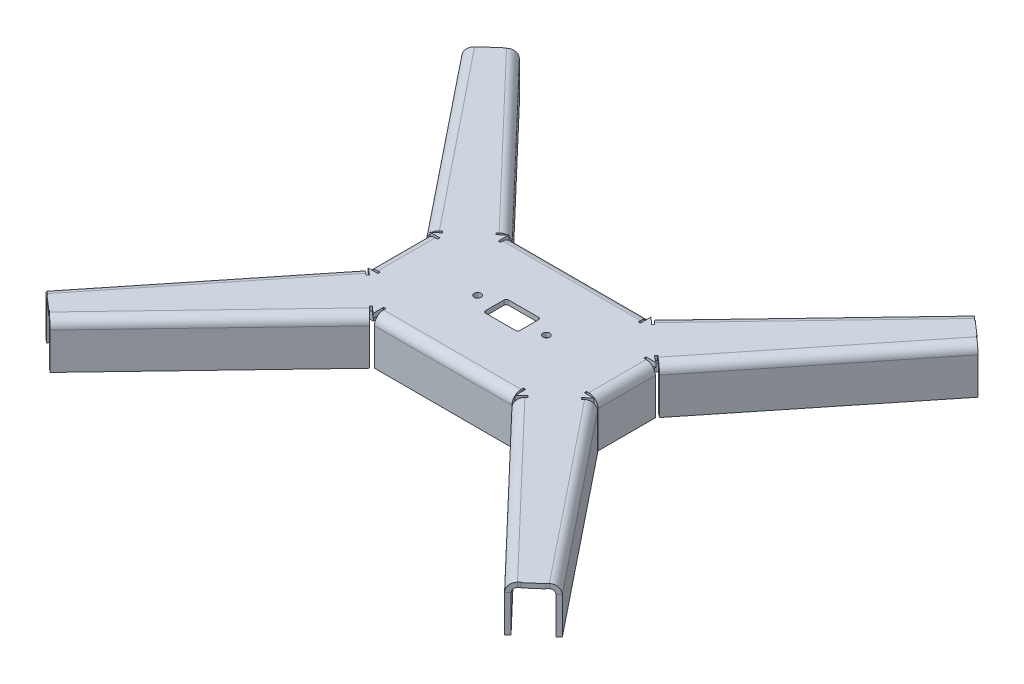
SolidWorks part; units mm, degrees
note: The reader was unsure of these and kept them because the rebuilt part matched: flange length of "Edge-Flange1", "Edge-Flange2", "Edge-Flange3", "Edge-Flange4", "Edge-Flange5", "Edge-Flange6", "Edge-Flange8", "Edge-Flange9", "Edge-Flange10", "Edge-Flange11", "Edge-Flange12", "Edge-Flange13".
material "1060 Alloy"
ref_plane "Front Plane" through (0, 0, 0) normal (0, 0, 1) x (1, 0, 0)
ref_plane "Top Plane" through (0, 0, 0) normal (0, 1, 0) x (1, 0, 0)
ref_plane "Right Plane" through (0, 0, 0) normal (1, 0, 0) x (0, 0, -1)
sketch "Sketch1" plane through (0, 0, 0) normal (0, 1, 0) x (1, 0, 0)
  line L0 (0, 0) -> (0, 30) construction
  line L1 (0, 0) -> (50, 0) construction
  line L2 (-30, 30) -> (30, 30)
  line L3 (30, 30) -> (50, 12.5) construction
  line L4 (50, 12.5) -> (50, -12.5)
  line L6 (-30, -30) -> (30, -30)
  line L9 (-50, 12.5) -> (-50, -12.5)
  line L10 (40, 21.25) -> (105.8505, 96.5077) construction
  line L11 (30, 30) -> (99.1363, 102.3826)
  line L12 (50, 12.5) -> (112.5646, 90.6328)
  line L13 (99.1363, 102.3826) -> (112.5646, 90.6328)
  line L14 (-40, 21.25) -> (-105.8505, 96.5077) construction
  line L15 (-30, 30) -> (-50, 12.5) construction
  line L16 (-99.1363, 102.3826) -> (-112.5646, 90.6328)
  line L17 (-50, 12.5) -> (-112.5646, 90.6328)
  line L18 (-30, 30) -> (-99.1363, 102.3826)
  line L19 (40, -21.25) -> (105.8505, -96.5077) construction
  line L20 (30, -30) -> (50, -12.5) construction
  line L21 (99.1363, -102.3826) -> (112.5646, -90.6328)
  line L22 (50, -12.5) -> (112.5646, -90.6328)
  line L23 (30, -30) -> (99.1363, -102.3826)
  line L24 (-30, -30) -> (-50, -12.5) construction
  line L25 (-40, -21.25) -> (-105.8505, -96.5077) construction
  line L26 (-30, -30) -> (-99.1363, -102.3826)
  line L27 (-50, -12.5) -> (-112.5646, -90.6328)
  line L28 (-99.1363, -102.3826) -> (-112.5646, -90.6328)
  dimension "D1" = 60
  dimension "D2" = 100
  dimension "D3" = 60
  dimension "D4" = 25
  dimension "D5" = 5
  dimension "D6" = 100
base flange "Base-Flange1" sketch "Sketch1" thickness 2 reverse thickness direction no parameters "D1"=2
edge flange "Edge-Flange1" sketch "Sketch8" flange angle 90 flange length 20 flange position material inside bend radius 2 thickness 2 relief rectangular parameters "D6"=10
sketch "Sketch8" plane through (0, -2, 30) normal (0, 0, 1) x (-1, 0, 0)
  line L0 (30, 0) -> (-30, 0) construction
  line L1 (30, 0) -> (-30, 0)
  line L2 (-30, 0) -> (-30, 18)
  line L3 (-30, 18) -> (30, 18)
  line L4 (30, 18) -> (30, 0)
bend "EdgeBend1" bend radius 2 bend angle 90 parameters "D5"=1
edge flange "Edge-Flange2" sketch "Sketch11" flange angle 90 flange length 20 flange position material inside bend radius 2 thickness 2 relief rectangular parameters "D6"=10
sketch "Sketch11" plane through (0, -2, -30) normal (0, 0, 1) x (-1, 0, 0)
  line L2 (-30, 0) -> (-30, 18)
  line L3 (-30, 18) -> (30, 18)
  line L4 (30, 18) -> (30, 0)
  line L5 (30, 0) -> (-30, 0) construction
  line L6 (30, 0) -> (-30, 0)
bend "EdgeBend2" bend radius 2 bend angle 90 parameters "D5"=2
edge flange "Edge-Flange3" sketch "Sketch19" flange angle 90 flange length 20 flange position material inside bend radius 2 thickness 2 relief rectangular parameters "D6"=10
sketch "Sketch19" plane through (50, -2, 0) normal (-1, 0, 0) x (0, 0, -1)
  line L2 (-12.5, 0) -> (-12.5, 18)
  line L3 (-12.5, 18) -> (12.5, 18)
  line L4 (12.5, 18) -> (12.5, 0)
  line L5 (12.5, 0) -> (-12.5, 0) construction
  line L6 (12.5, 0) -> (-12.5, 0)
bend "EdgeBend3" bend radius 2 bend angle 90 parameters "D5"=3
edge flange "Edge-Flange4" sketch "Sketch22" flange angle 90 flange length 20 flange position material inside bend radius 2 thickness 2 relief rectangular parameters "D6"=10
sketch "Sketch22" plane through (-50, -2, 0) normal (1, 0, 0) x (0, 0, 1)
  line L2 (-12.5, 0) -> (-12.5, 18)
  line L3 (-12.5, 18) -> (12.5, 18)
  line L4 (12.5, 18) -> (12.5, 0)
  line L5 (12.5, 0) -> (-12.5, 0) construction
  line L6 (12.5, 0) -> (-12.5, 0)
bend "EdgeBend4" bend radius 2 bend angle 90 parameters "D5"=4
edge flange "Edge-Flange5" sketch "Sketch26" flange angle 90 flange length 20 flange position material inside bend radius 2 thickness 2 relief rectangular parameters "D6"=10
sketch "Sketch26" plane through (24.3668, -2, -19.5116) normal (-0.7806, 0, 0.6251) x (-0.6251, 0, -0.7806)
  line L2 (-141.1051, 0) -> (-141.1051, 18)
  line L3 (-141.1051, 18) -> (-42.2909, 18)
  line L4 (-42.2909, 18) -> (-42.2909, 0)
  line L5 (-42.2909, 0) -> (-141.1051, 0) construction
  line L6 (-42.2909, 0) -> (-141.1051, 0)
bend "EdgeBend5" bend radius 2 bend angle 90 parameters "D5"=5
edge flange "Edge-Flange6" sketch "Sketch29" flange angle 90 flange length 20 flange position material inside bend radius 2 thickness 2 relief rectangular parameters "D6"=10
sketch "Sketch29" plane through (0.7036, -2, -0.672) normal (0.7231, 0, -0.6907) x (0.6907, 0, 0.7231)
  line L2 (43.863, 0) -> (43.863, 18)
  line L3 (43.863, 18) -> (142.5105, 18)
  line L4 (142.5105, 18) -> (142.5105, 0)
  line L5 (142.5105, 0) -> (43.863, 0) construction
  line L6 (142.5105, 0) -> (43.863, 0)
bend "EdgeBend6" bend radius 2 bend angle 90 parameters "D5"=6
edge flange "Edge-Flange8" sketch "Sketch39" flange angle 90 flange length 20 flange position material inside bend radius 2 thickness 2 relief rectangular parameters "D6"=10
sketch "Sketch39" plane through (24.3668, -2, 19.5116) normal (-0.7806, 0, -0.6251) x (0.6251, 0, -0.7806)
  line L2 (42.2909, 0) -> (42.2909, 18)
  line L3 (42.2909, 18) -> (141.1051, 18)
  line L4 (141.1051, 18) -> (141.1051, 0)
  line L5 (141.1051, 0) -> (42.2909, 0) construction
  line L6 (141.1051, 0) -> (42.2909, 0)
bend "EdgeBend8" bend radius 2 bend angle 90 parameters "D5"=7
edge flange "Edge-Flange9" sketch "Sketch42" flange angle 90 flange length 20 flange position material inside bend radius 2 thickness 2 relief rectangular parameters "D6"=10
sketch "Sketch42" plane through (0.7036, -2, 0.672) normal (0.7231, 0, 0.6907) x (-0.6907, 0, 0.7231)
  line L2 (-142.5105, 0) -> (-142.5105, 18)
  line L3 (-142.5105, 18) -> (-43.863, 18)
  line L4 (-43.863, 18) -> (-43.863, 0)
  line L5 (-43.863, 0) -> (-142.5105, 0) construction
  line L6 (-43.863, 0) -> (-142.5105, 0)
bend "EdgeBend9" bend radius 2 bend angle 90 parameters "D5"=8
edge flange "Edge-Flange10" sketch "Sketch45" flange angle 90 flange length 20 flange position material inside bend radius 2 thickness 2 relief rectangular parameters "D6"=10
sketch "Sketch45" plane through (-0.7036, -2, 0.672) normal (-0.7231, 0, 0.6907) x (-0.6907, 0, -0.7231)
  line L2 (43.863, 0) -> (43.863, 18)
  line L3 (43.863, 18) -> (142.5105, 18)
  line L4 (142.5105, 18) -> (142.5105, 0)
  line L5 (142.5105, 0) -> (43.863, 0) construction
  line L6 (142.5105, 0) -> (43.863, 0)
bend "EdgeBend10" bend radius 2 bend angle 90 parameters "D5"=9
edge flange "Edge-Flange11" sketch "Sketch48" flange angle 90 flange length 20 flange position material inside bend radius 2 thickness 2 relief rectangular parameters "D6"=10
sketch "Sketch48" plane through (-24.3668, -2, 19.5116) normal (0.7806, 0, -0.6251) x (0.6251, 0, 0.7806)
  line L2 (-141.1051, 0) -> (-141.1051, 18)
  line L3 (-141.1051, 18) -> (-42.2909, 18)
  line L4 (-42.2909, 18) -> (-42.2909, 0)
  line L5 (-42.2909, 0) -> (-141.1051, 0) construction
  line L6 (-42.2909, 0) -> (-141.1051, 0)
bend "EdgeBend11" bend radius 2 bend angle 90 parameters "D5"=10
edge flange "Edge-Flange12" sketch "Sketch51" flange angle 90 flange length 20 flange position material inside bend radius 2 thickness 2 relief rectangular parameters "D6"=10
sketch "Sketch51" plane through (-24.3668, -2, -19.5116) normal (0.7806, 0, 0.6251) x (-0.6251, 0, 0.7806)
  line L2 (42.2909, 0) -> (42.2909, 18)
  line L3 (42.2909, 18) -> (141.1051, 18)
  line L4 (141.1051, 18) -> (141.1051, 0)
  line L5 (141.1051, 0) -> (42.2909, 0) construction
  line L6 (141.1051, 0) -> (42.2909, 0)
bend "EdgeBend12" bend radius 2 bend angle 90 parameters "D5"=11
edge flange "Edge-Flange13" sketch "Sketch54" flange angle 90 flange length 20 flange position material inside bend radius 2 thickness 2 relief rectangular parameters "D6"=10
sketch "Sketch54" plane through (-0.7036, -2, -0.672) normal (-0.7231, 0, -0.6907) x (0.6907, 0, -0.7231)
  line L2 (-142.5105, 0) -> (-142.5105, 18)
  line L3 (-142.5105, 18) -> (-43.863, 18)
  line L4 (-43.863, 18) -> (-43.863, 0)
  line L5 (-43.863, 0) -> (-142.5105, 0) construction
  line L6 (-43.863, 0) -> (-142.5105, 0)
bend "EdgeBend13" bend radius 2 bend angle 90 parameters "D5"=12
sketch "Sketch58" plane through (0, 0, 0) normal (0, 1, 0) x (1, 0, 0)
  circle A0 centre (15, 0) radius 1.25 construction
  circle A1 centre (-15, 0) radius 1.25 construction
  circle A2 centre (15, 0) radius 1.25 construction
  circle A3 centre (-15, 0) radius 1.25 construction
  circle A4 centre (-15, 0) radius 1.5
  circle A5 centre (15, 0) radius 1.5
  dimension "D1" = 0.25
  dimension "D2" = 0.25
extrude "Cut-Extrude2" cut sketch "Sketch58" against normal through all normal cut yes
sketch "Sketch59" plane through (0, -2, 0) normal (0, -1, 0) x (1, 0, 0)
  line L1 (-7.5, -5) -> (7.5, -5)
  line L2 (-7.5, -5) -> (-7.5, 5)
  line L3 (-7.5, 5) -> (7.5, 5)
  line L4 (7.5, -5) -> (7.5, 5)
  line L5 (-7.5, -5) -> (7.5, 5) construction
  line L6 (-7.5, 5) -> (7.5, -5) construction
  point P0 (0, 0)
  dimension "D1" = 10
  dimension "D2" = 15
extrude "Cut-Extrude3" cut sketch "Sketch59" against normal through all normal cut yes
fillet "Fillet1" radius 1 4 edges at (-7.5, -1, 5) (-7.5, -1, -5) (7.5, -1, -5) (7.5, -1, 5)
sketch "Bend-Lines1" [suppressed] plane through (0, 0, 0) normal (0, 1, 0) x (1, 0, 0)
sketch "Bounding-Box1" [suppressed] plane through (0, 0, 0) normal (0, 1, 0) x (1, 0, 0)
sheet metal parameters "Sheet-Metal1" thickness 2 parameters "D1"=2
flat pattern "Flat-Pattern1" [suppressed]
sketch "Bend-Lines2" plane through (0, 0, 0) normal (0, 1, 0) x (1, 0, 0)
sketch3d "Bounding-Box2" [suppressed]
  line L0 (-50, 30, 0) -> (50, 30, 0) construction
  line L1 (-50, -30, 0) -> (50, -30, 0) construction
  line L2 (-50, 30, 0) -> (-50, -30, 0) construction
  line L3 (50, 30, 0) -> (50, -30, 0) construction
sheet metal parameters "Sheet-Metal2" thickness 2 parameters "D1"=2
flat pattern "Flat-Pattern1"
sketch "Bend-Lines2" plane through (0, 0, 0) normal (0, 1, 0) x (1, 0, 0)
  line L0 (-30, -28.3562) -> (30, -28.3562) construction
  line L1 (-30, -28.3562) -> (30, -28.3562) construction
sketch3d "Bounding-Box2" [suppressed]
  line L0 (50, 30, 0) -> (-50, 30, 0) construction
  line L1 (50, -46.7124, 0) -> (-50, -46.7124, 0) construction
  line L2 (50, 30, 0) -> (50, -46.7124, 0) construction
  line L3 (-50, 30, 0) -> (-50, -46.7124, 0) construction
bend of the flat pattern "Flatten-<EdgeBend1>1"
sheet metal parameters "Sheet-Metal3" thickness 2 parameters "D1"=2
flat pattern "Flat-Pattern1" [suppressed]
sketch "Bend-Lines2" plane through (0, 0, 0) normal (0, 1, 0) x (1, 0, 0)
  line L0 (-30, -28.3562) -> (30, -28.3562) construction
  line L1 (-30, -28.3562) -> (30, -28.3562) construction
  line L2 (30, 28.3562) -> (-30, 28.3562) construction
  line L3 (30, 28.3562) -> (-30, 28.3562) construction
sketch3d "Bounding-Box2" [suppressed]
  line L0 (50, 46.7124, 0) -> (-50, 46.7124, 0) construction
  line L1 (50, -46.7124, 0) -> (-50, -46.7124, 0) construction
  line L2 (50, 46.7124, 0) -> (50, -46.7124, 0) construction
  line L3 (-50, 46.7124, 0) -> (-50, -46.7124, 0) construction
bend of the flat pattern "Flatten-<EdgeBend1>1"
bend of the flat pattern "Flatten-<EdgeBend2>1"
sheet metal parameters "Sheet-Metal4" thickness 2 parameters "D1"=2
flat pattern "Flat-Pattern1" [suppressed]
sketch "Bend-Lines2" plane through (0, 0, 0) normal (0, 1, 0) x (1, 0, 0)
  line L0 (-30, -28.3562) -> (30, -28.3562) construction
  line L1 (-30, -28.3562) -> (30, -28.3562) construction
  line L2 (30, 28.3562) -> (-30, 28.3562) construction
  line L3 (30, 28.3562) -> (-30, 28.3562) construction
  line L4 (48.3562, -12.5) -> (48.3562, 12.5) construction
  line L5 (48.3562, -12.5) -> (48.3562, 12.5) construction
sketch3d "Bounding-Box2" [suppressed]
  line L0 (66.7124, 46.7124, 0) -> (-50, 46.7124, 0) construction
  line L1 (66.7124, -46.7124, 0) -> (-50, -46.7124, 0) construction
  line L2 (66.7124, 46.7124, 0) -> (66.7124, -46.7124, 0) construction
  line L3 (-50, 46.7124, 0) -> (-50, -46.7124, 0) construction
bend of the flat pattern "Flatten-<EdgeBend1>1"
bend of the flat pattern "Flatten-<EdgeBend3>1"
bend of the flat pattern "Flatten-<EdgeBend2>1"
sheet metal parameters "Sheet-Metal5" thickness 2 parameters "D1"=2
flat pattern "Flat-Pattern1" [suppressed]
sketch "Bend-Lines2" plane through (0, 0, 0) normal (0, 1, 0) x (1, 0, 0)
  line L0 (-30, -28.3562) -> (30, -28.3562) construction
  line L1 (-30, -28.3562) -> (30, -28.3562) construction
  line L2 (30, 28.3562) -> (-30, 28.3562) construction
  line L3 (30, 28.3562) -> (-30, 28.3562) construction
  line L4 (48.3562, -12.5) -> (48.3562, 12.5) construction
  line L5 (48.3562, -12.5) -> (48.3562, 12.5) construction
  line L6 (-48.3562, 12.5) -> (-48.3562, -12.5) construction
  line L7 (-48.3562, 12.5) -> (-48.3562, -12.5) construction
sketch3d "Bounding-Box2" [suppressed]
  line L0 (110.9178, -100.9416, 0) -> (-110.9178, -100.9416, 0) construction
  line L1 (110.9178, 100.9416, 0) -> (-110.9178, 100.9416, 0) construction
  line L2 (110.9178, -100.9416, 0) -> (110.9178, 100.9416, 0) construction
  line L3 (-110.9178, -100.9416, 0) -> (-110.9178, 100.9416, 0) construction
bend of the flat pattern "Flatten-<EdgeBend1>1"
bend of the flat pattern "Flatten-<EdgeBend3>1"
bend of the flat pattern "Flatten-<EdgeBend4>1"
bend of the flat pattern "Flatten-<EdgeBend2>1"
sheet metal parameters "Sheet-Metal6" thickness 2 parameters "D1"=2
flat pattern "Flat-Pattern1" [suppressed]
sketch "Bend-Lines2" plane through (0, 0, 0) normal (0, 1, 0) x (1, 0, 0)
  line L0 (-30, -28.3562) -> (30, -28.3562) construction
  line L1 (-30, -28.3562) -> (30, -28.3562) construction
  line L2 (30, 28.3562) -> (-30, 28.3562) construction
  line L3 (30, 28.3562) -> (-30, 28.3562) construction
  line L4 (48.3562, -12.5) -> (48.3562, 12.5) construction
  line L5 (48.3562, -12.5) -> (48.3562, 12.5) construction
  line L6 (-48.3562, 12.5) -> (-48.3562, -12.5) construction
  line L7 (-48.3562, 12.5) -> (-48.3562, -12.5) construction
  line L8 (109.6126, -93.073) -> (49.4603, -14.4992) construction
  line L9 (109.6126, -93.073) -> (49.4603, -14.4992) construction
sketch3d "Bounding-Box2" [suppressed]
  line L0 (124.188, -100.9416, 0) -> (-110.9178, -100.9416, 0) construction
  line L1 (124.188, 100.9416, 0) -> (-110.9178, 100.9416, 0) construction
  line L2 (124.188, -100.9416, 0) -> (124.188, 100.9416, 0) construction
  line L3 (-110.9178, -100.9416, 0) -> (-110.9178, 100.9416, 0) construction
bend of the flat pattern "Flatten-<EdgeBend1>1"
bend of the flat pattern "Flatten-<EdgeBend3>1"
bend of the flat pattern "Flatten-<EdgeBend4>1"
bend of the flat pattern "Flatten-<EdgeBend5>1"
bend of the flat pattern "Flatten-<EdgeBend2>1"
sheet metal parameters "Sheet-Metal7" thickness 2 parameters "D1"=2
flat pattern "Flat-Pattern1" [suppressed]
sketch "Bend-Lines2" plane through (0, 0, 0) normal (0, 1, 0) x (1, 0, 0)
  line L0 (-30, -28.3562) -> (30, -28.3562) construction
  line L1 (-30, -28.3562) -> (30, -28.3562) construction
  line L2 (30, 28.3562) -> (-30, 28.3562) construction
  line L3 (30, 28.3562) -> (-30, 28.3562) construction
  line L4 (48.3562, -12.5) -> (48.3562, 12.5) construction
  line L5 (48.3562, -12.5) -> (48.3562, 12.5) construction
  line L6 (-48.3562, 12.5) -> (-48.3562, -12.5) construction
  line L7 (-48.3562, 12.5) -> (-48.3562, -12.5) construction
  line L8 (109.6126, -93.073) -> (49.4603, -14.4992) construction
  line L9 (109.6126, -93.073) -> (49.4603, -14.4992) construction
  line L10 (32.1636, -29.8412) -> (101.9468, -99.7806) construction
  line L11 (32.1636, -29.8412) -> (101.9468, -99.7806) construction
sketch3d "Bounding-Box2" [suppressed]
  line L0 (124.188, -112.7458, 0) -> (-110.9178, -112.7458, 0) construction
  line L1 (124.188, 100.9416, 0) -> (-110.9178, 100.9416, 0) construction
  line L2 (124.188, -112.7458, 0) -> (124.188, 100.9416, 0) construction
  line L3 (-110.9178, -112.7458, 0) -> (-110.9178, 100.9416, 0) construction
bend of the flat pattern "Flatten-<EdgeBend1>1"
bend of the flat pattern "Flatten-<EdgeBend3>1"
bend of the flat pattern "Flatten-<EdgeBend4>1"
bend of the flat pattern "Flatten-<EdgeBend5>1"
bend of the flat pattern "Flatten-<EdgeBend6>1"
bend of the flat pattern "Flatten-<EdgeBend2>1"
sheet metal parameters "Sheet-Metal9" thickness 2 parameters "D1"=2
flat pattern "Flat-Pattern1" [suppressed]
sketch "Bend-Lines2" plane through (0, 0, 0) normal (0, 1, 0) x (1, 0, 0)
  line L0 (-30, -28.3562) -> (30, -28.3562) construction
  line L1 (-30, -28.3562) -> (30, -28.3562) construction
  line L2 (30, 28.3562) -> (-30, 28.3562) construction
  line L3 (30, 28.3562) -> (-30, 28.3562) construction
  line L4 (48.3562, -12.5) -> (48.3562, 12.5) construction
  line L5 (48.3562, -12.5) -> (48.3562, 12.5) construction
  line L6 (-48.3562, 12.5) -> (-48.3562, -12.5) construction
  line L7 (-48.3562, 12.5) -> (-48.3562, -12.5) construction
  line L8 (109.6126, -93.073) -> (49.4603, -14.4992) construction
  line L9 (109.6126, -93.073) -> (49.4603, -14.4992) construction
  line L10 (32.1636, -29.8412) -> (101.9468, -99.7806) construction
  line L11 (32.1636, -29.8412) -> (101.9468, -99.7806) construction
  line L12 (49.4603, 14.4992) -> (109.6126, 93.073) construction
  line L13 (49.4603, 14.4992) -> (109.6126, 93.073) construction
sketch3d "Bounding-Box2" [suppressed]
  line L0 (124.188, -112.7458, 0) -> (-110.9178, -112.7458, 0) construction
  line L1 (124.188, 100.9416, 0) -> (-110.9178, 100.9416, 0) construction
  line L2 (124.188, -112.7458, 0) -> (124.188, 100.9416, 0) construction
  line L3 (-110.9178, -112.7458, 0) -> (-110.9178, 100.9416, 0) construction
bend of the flat pattern "Flatten-<EdgeBend1>1"
bend of the flat pattern "Flatten-<EdgeBend3>1"
bend of the flat pattern "Flatten-<EdgeBend4>1"
bend of the flat pattern "Flatten-<EdgeBend5>1"
bend of the flat pattern "Flatten-<EdgeBend6>1"
bend of the flat pattern "Flatten-<EdgeBend8>1"
bend of the flat pattern "Flatten-<EdgeBend2>1"
sheet metal parameters "Sheet-Metal10" thickness 2 parameters "D1"=2
flat pattern "Flat-Pattern1" [suppressed]
sketch "Bend-Lines2" plane through (0, 0, 0) normal (0, 1, 0) x (1, 0, 0)
  line L0 (-30, -28.3562) -> (30, -28.3562) construction
  line L1 (-30, -28.3562) -> (30, -28.3562) construction
  line L2 (30, 28.3562) -> (-30, 28.3562) construction
  line L3 (30, 28.3562) -> (-30, 28.3562) construction
  line L4 (48.3562, -12.5) -> (48.3562, 12.5) construction
  line L5 (48.3562, -12.5) -> (48.3562, 12.5) construction
  line L6 (-48.3562, 12.5) -> (-48.3562, -12.5) construction
  line L7 (-48.3562, 12.5) -> (-48.3562, -12.5) construction
  line L8 (109.6126, -93.073) -> (49.4603, -14.4992) construction
  line L9 (109.6126, -93.073) -> (49.4603, -14.4992) construction
  line L10 (32.1636, -29.8412) -> (101.9468, -99.7806) construction
  line L11 (32.1636, -29.8412) -> (101.9468, -99.7806) construction
  line L12 (49.4603, 14.4992) -> (109.6126, 93.073) construction
  line L13 (49.4603, 14.4992) -> (109.6126, 93.073) construction
  line L14 (101.9468, 99.7806) -> (32.1636, 29.8412) construction
  line L15 (101.9468, 99.7806) -> (32.1636, 29.8412) construction
sketch3d "Bounding-Box2" [suppressed]
  line L0 (124.188, -112.7458, 0) -> (-110.9178, -112.7458, 0) construction
  line L1 (124.188, 112.7458, 0) -> (-110.9178, 112.7458, 0) construction
  line L2 (124.188, -112.7458, 0) -> (124.188, 112.7458, 0) construction
  line L3 (-110.9178, -112.7458, 0) -> (-110.9178, 112.7458, 0) construction
bend of the flat pattern "Flatten-<EdgeBend1>1"
bend of the flat pattern "Flatten-<EdgeBend3>1"
bend of the flat pattern "Flatten-<EdgeBend4>1"
bend of the flat pattern "Flatten-<EdgeBend5>1"
bend of the flat pattern "Flatten-<EdgeBend6>1"
bend of the flat pattern "Flatten-<EdgeBend8>1"
bend of the flat pattern "Flatten-<EdgeBend9>1"
bend of the flat pattern "Flatten-<EdgeBend2>1"
sheet metal parameters "Sheet-Metal11" thickness 2 parameters "D1"=2
flat pattern "Flat-Pattern1"
sketch "Bend-Lines2" plane through (0, 0, 0) normal (0, 1, 0) x (1, 0, 0)
  line L0 (-30, -28.3562) -> (30, -28.3562) construction
  line L1 (-30, -28.3562) -> (30, -28.3562) construction
  line L2 (30, 28.3562) -> (-30, 28.3562) construction
  line L3 (30, 28.3562) -> (-30, 28.3562) construction
  line L4 (48.3562, -12.5) -> (48.3562, 12.5) construction
  line L5 (48.3562, -12.5) -> (48.3562, 12.5) construction
  line L6 (-48.3562, 12.5) -> (-48.3562, -12.5) construction
  line L7 (-48.3562, 12.5) -> (-48.3562, -12.5) construction
  line L8 (111.2815, -91.6602) -> (49.5176, -14.5275) construction
  line L9 (111.2815, -91.6602) -> (49.5176, -14.5275) construction
  line L10 (32.1887, -29.9116) -> (100.325, -101.2472) construction
  line L11 (32.1887, -29.9116) -> (100.325, -101.2472) construction
  line L12 (49.5176, 14.5275) -> (111.2815, 91.6602) construction
  line L13 (49.5176, 14.5275) -> (111.2815, 91.6602) construction
  line L14 (100.325, 101.2472) -> (32.1887, 29.9116) construction
  line L15 (100.325, 101.2472) -> (32.1887, 29.9116) construction
  line L16 (-32.1887, 29.9116) -> (-100.325, 101.2472) construction
  line L17 (-32.1887, 29.9116) -> (-100.325, 101.2472) construction
sketch3d "Bounding-Box2" [suppressed]
  line L0 (125.6101, -113.9259, 0) -> (-112.5646, -113.9259, 0) construction
  line L1 (125.6101, 113.9259, 0) -> (-112.5646, 113.9259, 0) construction
  line L2 (125.6101, -113.9259, 0) -> (125.6101, 113.9259, 0) construction
  line L3 (-112.5646, -113.9259, 0) -> (-112.5646, 113.9259, 0) construction
bend of the flat pattern "Flatten-<EdgeBend1>1"
bend of the flat pattern "Flatten-<EdgeBend3>1"
bend of the flat pattern "Flatten-<EdgeBend4>1"
bend of the flat pattern "Flatten-<EdgeBend5>1"
bend of the flat pattern "Flatten-<EdgeBend6>1"
bend of the flat pattern "Flatten-<EdgeBend8>1"
bend of the flat pattern "Flatten-<EdgeBend9>1"
bend of the flat pattern "Flatten-<EdgeBend10>1"
bend of the flat pattern "Flatten-<EdgeBend2>1"
sheet metal parameters "Sheet-Metal12" thickness 2 parameters "D1"=2
flat pattern "Flat-Pattern1"
sketch "Bend-Lines2" plane through (0, 0, 0) normal (0, 1, 0) x (1, 0, 0)
  line L0 (-30, -28.3562) -> (30, -28.3562) construction
  line L1 (-30, -28.3562) -> (30, -28.3562) construction
  line L2 (30, 28.3562) -> (-30, 28.3562) construction
  line L3 (30, 28.3562) -> (-30, 28.3562) construction
  line L4 (48.3562, -12.5) -> (48.3562, 12.5) construction
  line L5 (48.3562, -12.5) -> (48.3562, 12.5) construction
  line L6 (-48.3562, 12.5) -> (-48.3562, -12.5) construction
  line L7 (-48.3562, 12.5) -> (-48.3562, -12.5) construction
  line L8 (111.2815, -91.6602) -> (49.5176, -14.5275) construction
  line L9 (111.2815, -91.6602) -> (49.5176, -14.5275) construction
  line L10 (32.1887, -29.9116) -> (100.325, -101.2472) construction
  line L11 (32.1887, -29.9116) -> (100.325, -101.2472) construction
  line L12 (49.5176, 14.5275) -> (111.2815, 91.6602) construction
  line L13 (49.5176, 14.5275) -> (111.2815, 91.6602) construction
  line L14 (100.325, 101.2472) -> (32.1887, 29.9116) construction
  line L15 (100.325, 101.2472) -> (32.1887, 29.9116) construction
  line L16 (-32.1887, 29.9116) -> (-100.325, 101.2472) construction
  line L17 (-32.1887, 29.9116) -> (-100.325, 101.2472) construction
  line L18 (-112.8427, 90.4101) -> (-51.0788, 13.2774) construction
  line L19 (-112.8427, 90.4101) -> (-51.0788, 13.2774) construction
sketch3d "Bounding-Box2" [suppressed]
  line L0 (125.6101, -113.9259, 0) -> (-127.1712, -113.9259, 0) construction
  line L1 (125.6101, 113.9259, 0) -> (-127.1712, 113.9259, 0) construction
  line L2 (125.6101, -113.9259, 0) -> (125.6101, 113.9259, 0) construction
  line L3 (-127.1712, -113.9259, 0) -> (-127.1712, 113.9259, 0) construction
bend of the flat pattern "Flatten-<EdgeBend1>1"
bend of the flat pattern "Flatten-<EdgeBend3>1"
bend of the flat pattern "Flatten-<EdgeBend4>1"
bend of the flat pattern "Flatten-<EdgeBend5>1"
bend of the flat pattern "Flatten-<EdgeBend6>1"
bend of the flat pattern "Flatten-<EdgeBend8>1"
bend of the flat pattern "Flatten-<EdgeBend9>1"
bend of the flat pattern "Flatten-<EdgeBend10>1"
bend of the flat pattern "Flatten-<EdgeBend2>1"
bend of the flat pattern "Flatten-<EdgeBend11>1"
sheet metal parameters "Sheet-Metal13" thickness 2 parameters "D1"=2
flat pattern "Flat-Pattern1"
sketch "Bend-Lines2" plane through (0, 0, 0) normal (0, 1, 0) x (1, 0, 0)
  line L0 (-30, -28.3562) -> (30, -28.3562) construction
  line L1 (-30, -28.3562) -> (30, -28.3562) construction
  line L2 (30, 28.3562) -> (-30, 28.3562) construction
  line L3 (30, 28.3562) -> (-30, 28.3562) construction
  line L4 (48.3562, -12.5) -> (48.3562, 12.5) construction
  line L5 (48.3562, -12.5) -> (48.3562, 12.5) construction
  line L6 (-48.3562, 12.5) -> (-48.3562, -12.5) construction
  line L7 (-48.3562, 12.5) -> (-48.3562, -12.5) construction
  line L8 (111.2815, -91.6602) -> (49.5176, -14.5275) construction
  line L9 (111.2815, -91.6602) -> (49.5176, -14.5275) construction
  line L10 (32.1887, -29.9116) -> (100.325, -101.2472) construction
  line L11 (32.1887, -29.9116) -> (100.325, -101.2472) construction
  line L12 (49.5176, 14.5275) -> (111.2815, 91.6602) construction
  line L13 (49.5176, 14.5275) -> (111.2815, 91.6602) construction
  line L14 (100.325, 101.2472) -> (32.1887, 29.9116) construction
  line L15 (100.325, 101.2472) -> (32.1887, 29.9116) construction
  line L16 (-32.1887, 29.9116) -> (-100.325, 101.2472) construction
  line L17 (-32.1887, 29.9116) -> (-100.325, 101.2472) construction
  line L18 (-112.8427, 90.4101) -> (-51.0788, 13.2774) construction
  line L19 (-112.8427, 90.4101) -> (-51.0788, 13.2774) construction
  line L20 (-51.0788, -13.2774) -> (-112.8427, -90.4101) construction
  line L21 (-51.0788, -13.2774) -> (-112.8427, -90.4101) construction
sketch3d "Bounding-Box2" [suppressed]
  line L0 (125.6101, -113.9259, 0) -> (-127.1712, -113.9259, 0) construction
  line L1 (125.6101, 113.9259, 0) -> (-127.1712, 113.9259, 0) construction
  line L2 (125.6101, -113.9259, 0) -> (125.6101, 113.9259, 0) construction
  line L3 (-127.1712, -113.9259, 0) -> (-127.1712, 113.9259, 0) construction
bend of the flat pattern "Flatten-<EdgeBend1>1"
bend of the flat pattern "Flatten-<EdgeBend3>1"
bend of the flat pattern "Flatten-<EdgeBend4>1"
bend of the flat pattern "Flatten-<EdgeBend5>1"
bend of the flat pattern "Flatten-<EdgeBend6>1"
bend of the flat pattern "Flatten-<EdgeBend8>1"
bend of the flat pattern "Flatten-<EdgeBend9>1"
bend of the flat pattern "Flatten-<EdgeBend10>1"
bend of the flat pattern "Flatten-<EdgeBend2>1"
bend of the flat pattern "Flatten-<EdgeBend11>1"
bend of the flat pattern "Flatten-<EdgeBend12>1"
sheet metal parameters "Sheet-Metal14" thickness 2 parameters "D1"=2
flat pattern "Flat-Pattern1"
sketch "Bend-Lines2" plane through (0, 0, 0) normal (0, 1, 0) x (1, 0, 0)
  line L0 (-30, -28.3562) -> (30, -28.3562) construction
  line L1 (-30, -28.3562) -> (30, -28.3562) construction
  line L2 (30, 28.3562) -> (-30, 28.3562) construction
  line L3 (30, 28.3562) -> (-30, 28.3562) construction
  line L4 (48.3562, -12.5) -> (48.3562, 12.5) construction
  line L5 (48.3562, -12.5) -> (48.3562, 12.5) construction
  line L6 (-48.3562, 12.5) -> (-48.3562, -12.5) construction
  line L7 (-48.3562, 12.5) -> (-48.3562, -12.5) construction
  line L8 (111.2815, -91.6602) -> (49.5176, -14.5275) construction
  line L9 (111.2815, -91.6602) -> (49.5176, -14.5275) construction
  line L10 (32.1887, -29.9116) -> (100.325, -101.2472) construction
  line L11 (32.1887, -29.9116) -> (100.325, -101.2472) construction
  line L12 (49.5176, 14.5275) -> (111.2815, 91.6602) construction
  line L13 (49.5176, 14.5275) -> (111.2815, 91.6602) construction
  line L14 (100.325, 101.2472) -> (32.1887, 29.9116) construction
  line L15 (100.325, 101.2472) -> (32.1887, 29.9116) construction
  line L16 (-32.1887, 29.9116) -> (-100.325, 101.2472) construction
  line L17 (-32.1887, 29.9116) -> (-100.325, 101.2472) construction
  line L18 (-112.8427, 90.4101) -> (-51.0788, 13.2774) construction
  line L19 (-112.8427, 90.4101) -> (-51.0788, 13.2774) construction
  line L20 (-51.0788, -13.2774) -> (-112.8427, -90.4101) construction
  line L21 (-51.0788, -13.2774) -> (-112.8427, -90.4101) construction
  line L22 (-98.8787, -102.6286) -> (-30.7424, -31.293) construction
  line L23 (-98.8787, -102.6286) -> (-30.7424, -31.293) construction
sketch3d "Bounding-Box2" [suppressed]
  line L0 (125.6101, -115.3073, 0) -> (-127.1712, -115.3073, 0) construction
  line L1 (125.6101, 113.9259, 0) -> (-127.1712, 113.9259, 0) construction
  line L2 (125.6101, -115.3073, 0) -> (125.6101, 113.9259, 0) construction
  line L3 (-127.1712, -115.3073, 0) -> (-127.1712, 113.9259, 0) construction
bend of the flat pattern "Flatten-<EdgeBend1>1"
bend of the flat pattern "Flatten-<EdgeBend3>1"
bend of the flat pattern "Flatten-<EdgeBend4>1"
bend of the flat pattern "Flatten-<EdgeBend5>1"
bend of the flat pattern "Flatten-<EdgeBend6>1"
bend of the flat pattern "Flatten-<EdgeBend8>1"
bend of the flat pattern "Flatten-<EdgeBend9>1"
bend of the flat pattern "Flatten-<EdgeBend10>1"
bend of the flat pattern "Flatten-<EdgeBend2>1"
bend of the flat pattern "Flatten-<EdgeBend11>1"
bend of the flat pattern "Flatten-<EdgeBend12>1"
bend of the flat pattern "Flatten-<EdgeBend13>1"
sheet metal parameters "Sheet-Metal19" thickness 2 parameters "D1"=2
flat pattern "Flat-Pattern1"
sketch "Bend-Lines2" plane through (0, 0, 0) normal (0, 1, 0) x (1, 0, 0)
  line L0 (-30, -28.3562) -> (30, -28.3562) construction
  line L1 (-30, -28.3562) -> (30, -28.3562) construction
  line L2 (30, 28.3562) -> (-30, 28.3562) construction
  line L3 (30, 28.3562) -> (-30, 28.3562) construction
  line L4 (48.3562, -12.5) -> (48.3562, 12.5) construction
  line L5 (48.3562, -12.5) -> (48.3562, 12.5) construction
  line L6 (-48.3562, 12.5) -> (-48.3562, -12.5) construction
  line L7 (-48.3562, 12.5) -> (-48.3562, -12.5) construction
  line L8 (111.2815, -91.6602) -> (49.5176, -14.5275) construction
  line L9 (111.2815, -91.6602) -> (49.5176, -14.5275) construction
  line L10 (32.1887, -29.9116) -> (100.325, -101.2472) construction
  line L11 (32.1887, -29.9116) -> (100.325, -101.2472) construction
  line L12 (49.5176, 14.5275) -> (111.2815, 91.6602) construction
  line L13 (49.5176, 14.5275) -> (111.2815, 91.6602) construction
  line L14 (100.325, 101.2472) -> (32.1887, 29.9116) construction
  line L15 (100.325, 101.2472) -> (32.1887, 29.9116) construction
  line L16 (-32.1887, 29.9116) -> (-100.325, 101.2472) construction
  line L17 (-32.1887, 29.9116) -> (-100.325, 101.2472) construction
  line L18 (-111.2815, 91.6602) -> (-49.5176, 14.5275) construction
  line L19 (-111.2815, 91.6602) -> (-49.5176, 14.5275) construction
  line L20 (-49.5176, -14.5275) -> (-111.2815, -91.6602) construction
  line L21 (-49.5176, -14.5275) -> (-111.2815, -91.6602) construction
  line L22 (-100.325, -101.2472) -> (-32.1887, -29.9116) construction
  line L23 (-100.325, -101.2472) -> (-32.1887, -29.9116) construction
sketch3d "Bounding-Box2" [suppressed]
  line L0 (125.6101, -113.9259, 0) -> (-125.6101, -113.9259, 0) construction
  line L1 (125.6101, 113.9259, 0) -> (-125.6101, 113.9259, 0) construction
  line L2 (125.6101, -113.9259, 0) -> (125.6101, 113.9259, 0) construction
  line L3 (-125.6101, -113.9259, 0) -> (-125.6101, 113.9259, 0) construction
bend of the flat pattern "Flatten-<EdgeBend1>1"
bend of the flat pattern "Flatten-<EdgeBend3>1"
bend of the flat pattern "Flatten-<EdgeBend4>1"
bend of the flat pattern "Flatten-<EdgeBend5>1"
bend of the flat pattern "Flatten-<EdgeBend6>1"
bend of the flat pattern "Flatten-<EdgeBend8>1"
bend of the flat pattern "Flatten-<EdgeBend9>1"
bend of the flat pattern "Flatten-<EdgeBend10>1"
bend of the flat pattern "Flatten-<EdgeBend2>1"
bend of the flat pattern "Flatten-<EdgeBend11>1"
bend of the flat pattern "Flatten-<EdgeBend12>1"
bend of the flat pattern "Flatten-<EdgeBend13>1"
sheet metal parameters "Sheet-Metal20" thickness 2 parameters "D1"=2
flat pattern "Flat-Pattern1"
sketch "Bend-Lines2" plane through (0, 0, 0) normal (0, 1, 0) x (1, 0, 0)
  line L0 (-30, -28.3562) -> (30, -28.3562) construction
  line L1 (-30, -28.3562) -> (30, -28.3562) construction
  line L2 (30, 28.3562) -> (-30, 28.3562) construction
  line L3 (30, 28.3562) -> (-30, 28.3562) construction
  line L4 (48.3562, -12.5) -> (48.3562, 12.5) construction
  line L5 (48.3562, -12.5) -> (48.3562, 12.5) construction
  line L6 (-48.3562, 12.5) -> (-48.3562, -12.5) construction
  line L7 (-48.3562, 12.5) -> (-48.3562, -12.5) construction
  line L8 (111.2815, -91.6602) -> (49.5176, -14.5275) construction
  line L9 (111.2815, -91.6602) -> (49.5176, -14.5275) construction
  line L10 (32.1887, -29.9116) -> (100.325, -101.2472) construction
  line L11 (32.1887, -29.9116) -> (100.325, -101.2472) construction
  line L12 (49.5176, 14.5275) -> (111.2815, 91.6602) construction
  line L13 (49.5176, 14.5275) -> (111.2815, 91.6602) construction
  line L14 (100.325, 101.2472) -> (32.1887, 29.9116) construction
  line L15 (100.325, 101.2472) -> (32.1887, 29.9116) construction
  line L16 (-32.1887, 29.9116) -> (-100.325, 101.2472) construction
  line L17 (-32.1887, 29.9116) -> (-100.325, 101.2472) construction
  line L18 (-111.2815, 91.6602) -> (-49.5176, 14.5275) construction
  line L19 (-111.2815, 91.6602) -> (-49.5176, 14.5275) construction
  line L20 (-49.5176, -14.5275) -> (-111.2815, -91.6602) construction
  line L21 (-49.5176, -14.5275) -> (-111.2815, -91.6602) construction
  line L22 (-100.325, -101.2472) -> (-32.1887, -29.9116) construction
  line L23 (-100.325, -101.2472) -> (-32.1887, -29.9116) construction
sketch3d "Bounding-Box2" [suppressed]
  line L0 (125.6101, -113.9259, 0) -> (-125.6101, -113.9259, 0) construction
  line L1 (125.6101, 113.9259, 0) -> (-125.6101, 113.9259, 0) construction
  line L2 (125.6101, -113.9259, 0) -> (125.6101, 113.9259, 0) construction
  line L3 (-125.6101, -113.9259, 0) -> (-125.6101, 113.9259, 0) construction
bend of the flat pattern "Flatten-<EdgeBend1>1"
bend of the flat pattern "Flatten-<EdgeBend3>1"
bend of the flat pattern "Flatten-<EdgeBend4>1"
bend of the flat pattern "Flatten-<EdgeBend5>1"
bend of the flat pattern "Flatten-<EdgeBend6>1"
bend of the flat pattern "Flatten-<EdgeBend8>1"
bend of the flat pattern "Flatten-<EdgeBend9>1"
bend of the flat pattern "Flatten-<EdgeBend10>1"
bend of the flat pattern "Flatten-<EdgeBend2>1"
bend of the flat pattern "Flatten-<EdgeBend11>1"
bend of the flat pattern "Flatten-<EdgeBend12>1"
bend of the flat pattern "Flatten-<EdgeBend13>1"
equation "\"H1\"=20"
equation "\"D7@Edge-Flange1\"=\"H1\""
equation "\"D7@Edge-Flange2\"=\"H1\""
equation "\"D7@Edge-Flange5\"=\"H1\""
equation "\"D7@Edge-Flange6\"=\"H1\""
equation "\"D7@Edge-Flange7\"=\"H1\""
equation "\"D7@Edge-Flange8\"=\"H1\""
equation "\"D7@Edge-Flange9\"=\"H1\""
equation "\"D7@Edge-Flange10\"=\"H1\""
equation "\"D7@Edge-Flange11\"=\"H1\""
equation "\"D7@Edge-Flange12\"=\"H1\""
equation "\"D7@Edge-Flange13\"=\"H1\""
